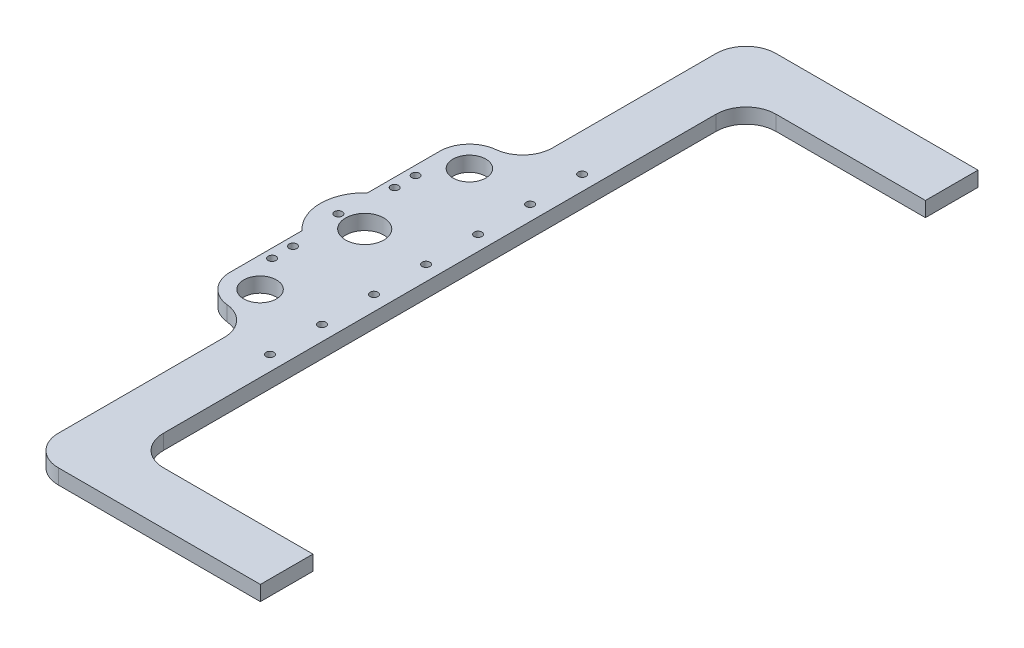
SolidWorks part; units mm, degrees
ref_plane "Front Plane" through (0, 0, 0) normal (0, 0, 1) x (1, 0, 0)
ref_plane "Top Plane" through (0, 0, 0) normal (0, 1, 0) x (1, 0, 0)
ref_plane "Right Plane" through (0, 0, 0) normal (1, 0, 0) x (0, 0, -1)
sketch "Sketch1" plane through (0, 0, 0) normal (0, 1, 0) x (1, 0, 0)
  line L0 (-67.9713, -52.7283) -> (-67.9713, -82.5864)
  line L1 (-45.2284, -108.5097) -> (-45.2284, -114.9973)
  line L3 (-22.9035, -128.2046) -> (-22.9035, 49.5954)
  line L5 (-45.2284, 37.4027) -> (-45.2284, 30.9152)
  line L6 (-67.9713, 4.9919) -> (-67.9713, -24.8662)
  line L7 (-45.2284, 49.5954) -> (-45.2284, 37.4027)
  line L13 (-22.9035, 49.5954) -> (-22.9035, 78.0705)
  line L14 (-22.9035, 113.0954) -> (-32.5284, 113.0954)
  line L15 (-45.2284, 49.5954) -> (-45.2284, 100.3954)
  line L16 (-45.2284, -114.9973) -> (-45.2284, -128.2046)
  line L19 (-45.2284, -128.2046) -> (-45.2284, -179.0046)
  line L20 (-32.5284, -191.7046) -> (-22.9035, -191.7046)
  line L21 (-22.9035, -128.2046) -> (-22.9035, -156.6798)
  line L22 (-22.9035, 113.0954) -> (53.2965, 113.0954)
  line L24 (-10.2035, 90.7705) -> (53.2965, 90.7705)
  line L25 (53.2965, 113.0954) -> (53.2965, 90.7705)
  line L26 (-22.9035, -191.7046) -> (53.2965, -191.7046)
  line L28 (-10.2035, -169.3798) -> (53.2965, -169.3798)
  line L29 (53.2965, -191.7046) -> (53.2965, -169.3798)
  arc A0 (-67.9713, -82.5864) -> (-56.6084, -95.8785) centre (-55.2885, -83.2473) ccw
  arc A1 (-45.2284, -108.5097) -> (-56.6084, -95.8785) centre (-57.9284, -108.5097) ccw
  arc A4 (-56.6084, 18.284) -> (-45.2284, 30.9152) centre (-57.9284, 30.9152) ccw
  arc A5 (-56.6084, 18.284) -> (-67.9713, 4.9919) centre (-55.2885, 5.6527) ccw
  arc A6 (-67.9713, -24.8662) -> (-67.9713, -52.7283) centre (-55.2885, -38.7973) ccw
  circle A7 centre (-55.2885, -38.7973) radius 8.128
  circle A8 centre (-55.2885, 5.6527) radius 6.985
  circle A9 centre (-55.2885, -83.2473) radius 6.985
  circle A10 centre (-29.2535, -38.7973) radius 1.651
  circle A11 centre (-29.2535, -16.6993) radius 1.651
  circle A12 centre (-29.2535, 5.3987) radius 1.651
  circle A13 centre (-29.2535, 27.4967) radius 1.651
  circle A14 centre (-29.2535, -60.8953) radius 1.651
  circle A15 centre (-29.2535, -82.9933) radius 1.651
  circle A16 centre (-29.2535, -105.0913) radius 1.651
  circle A17 centre (-66.4645, -38.7973) radius 1.651
  circle A18 centre (-64.1613, -60.3873) radius 1.651
  circle A19 centre (-64.1613, -69.2773) radius 1.651
  circle A20 centre (-64.1613, -17.2073) radius 1.651
  circle A21 centre (-64.1613, -8.3173) radius 1.651
  arc A22 (-45.2284, 100.3954) -> (-32.5284, 113.0954) centre (-32.5284, 100.3954) cw
  arc A23 (-45.2284, -179.0046) -> (-32.5284, -191.7046) centre (-32.5284, -179.0046) ccw
  arc A24 (-22.9035, 78.0705) -> (-10.2035, 90.7705) centre (-10.2035, 78.0705) cw
  arc A25 (-22.9035, -156.6798) -> (-10.2035, -169.3798) centre (-10.2035, -156.6798) ccw
  point P58 (-45.2284, 113.0954)
  dimension "D3" = 16.256
  dimension "D4" = 13.97
  dimension "D5" = 13.97
  dimension "D6" = 3.302
  dimension "D7" = 3.302
  dimension "D8" = 3.302
  dimension "D9" = 3.302
  dimension "D10" = 3.302
  dimension "D11" = 3.302
  dimension "D12" = 3.302
  dimension "D16" = 22.098
  dimension "D17" = 22.098
  dimension "D18" = 22.098
  dimension "D20" = 3.302
  dimension "D21" = 3.302
  dimension "D23" = 3.302
  dimension "D24" = 3.302
  dimension "D27" = 3.81
  dimension "D28" = 3.302
  dimension "D32" = 32.385
  dimension "D33" = 32.385
  dimension "D37" = 63.5
  dimension "D44" = 12.7
  dimension "D45" = 12.7
  dimension "D46" = 12.7
  dimension "D47" = 12.7
  dimension "D1" = 177.8
  dimension "D2" = 32.385
  dimension "D13" = 22.098
  dimension "D14" = 22.098
  dimension "D15" = 22.098
  dimension "D19" = 6.35
  dimension "D22" = 8.89
  dimension "D25" = 8.89
  dimension "D26" = 3.81
  dimension "D29" = 11.176
  dimension "D30" = 304.8
  dimension "D31" = 22.3249
  dimension "D34" = 13.97
  dimension "D35" = 21.59
  dimension "D36" = 22.3249
  dimension "D38" = 22.3249
  dimension "D39" = 22.3249
  dimension "D40" = 76.2
  dimension "D41" = 76.2
  dimension "D42" = 21.59
  dimension "D43" = 13.97
extrude "Boss-Extrude1" add sketch "Sketch1" along normal blind 6.35
